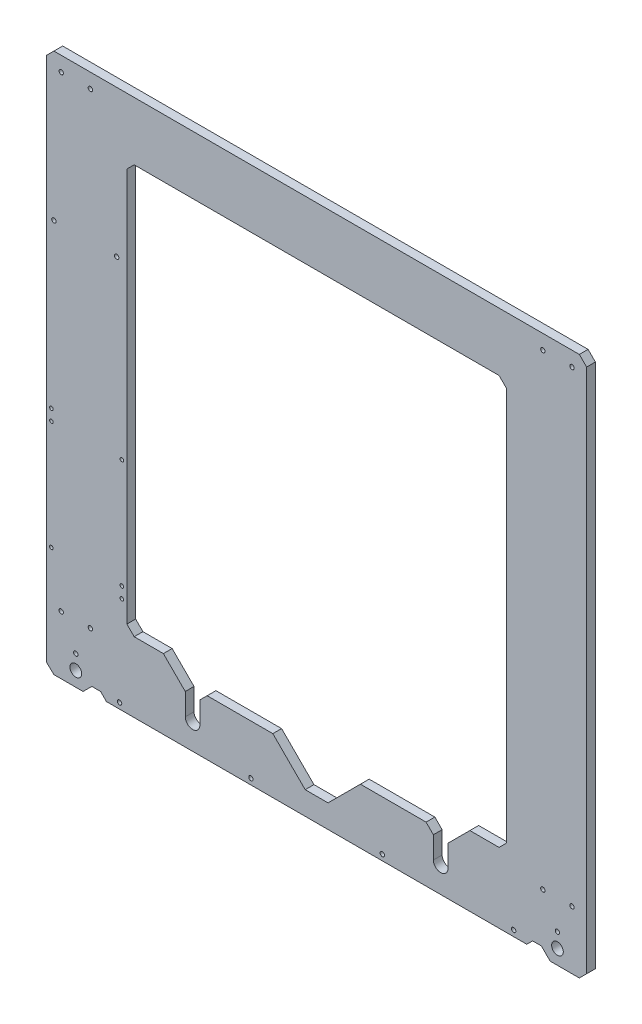
SolidWorks part; units mm, degrees
material "Lega 1060"
ref_plane "Piano frontale" through (0, 0, 0) normal (0, 0, 1) x (1, 0, 0)
ref_plane "Piano superiore" through (0, 0, 0) normal (0, 1, 0) x (1, 0, 0)
ref_plane "Piano destro" through (0, 0, 0) normal (1, 0, 0) x (0, 0, -1)
sketch "FRAME" plane through (0, 0, 0) normal (0, 0, 1) x (1, 0, 0)
  line L0 (0, 4.8083) -> (0, 365)
  line L1 (5, 370) -> (365, 370)
  line L2 (370, 365) -> (370, 5)
  line L3 (365, 0) -> (345, 0)
  line L4 (5, 0) -> (0, 4.8083)
  line L5 (0, 4.8083) -> (0, 365)
  line L6 (0, 365) -> (5, 370)
  line L7 (5, 370) -> (365, 370)
  line L8 (365, 370) -> (370, 365)
  line L9 (370, 365) -> (370, 5)
  line L10 (370, 5) -> (365, 0)
  line L11 (365, 0) -> (345, 0)
  line L12 (345, 0) -> (343, 2)
  line L13 (329, 2) -> (41, 2)
  line L14 (27, 2) -> (25, 0)
  line L15 (25, 0) -> (5, 0)
  line L16 (95, 20) -> (95, 35)
  line L17 (95, 35) -> (80, 50)
  line L18 (80, 50) -> (60, 50)
  line L19 (60, 50) -> (55, 55)
  line L20 (55, 55) -> (55, 325)
  line L21 (55, 325) -> (60, 330)
  line L22 (60, 330) -> (310, 330)
  line L23 (310, 330) -> (315, 325)
  line L24 (315, 325) -> (315, 55)
  line L25 (315, 55) -> (310, 50)
  line L26 (105, 20) -> (105, 35)
  line L27 (105, 35) -> (110, 40)
  line L28 (310, 50) -> (290, 50)
  line L29 (290, 50) -> (275, 35)
  line L30 (275, 35) -> (275, 20)
  line L31 (265, 20) -> (265, 35)
  line L32 (265, 35) -> (260, 40)
  line L33 (177.1751, 17.8249) -> (192.8249, 17.8249)
  line L34 (192.8249, 17.8249) -> (215, 40)
  line L35 (177.1751, 17.8249) -> (155, 40)
  line L36 (110, 40) -> (155, 40)
  line L37 (215, 40) -> (260, 40)
  line L105 (340, 360) -> (360, 360) construction
  line L178 (343, 2) -> (339, 6)
  line L179 (339, 6) -> (333, 6)
  line L180 (333, 6) -> (329, 2)
  line L181 (27, 2) -> (31, 6)
  line L182 (31, 6) -> (37, 6)
  line L183 (37, 6) -> (41, 2)
  line L196 (25, 0) -> (5, 0)
  line L198 (355, 0) -> (404.0551, 0) construction
  line L199 (290, 370) -> (404.0551, 370) construction
  arc A0 (95, 20) -> (105, 20) centre (100, 20) ccw
  arc A1 (265, 20) -> (275, 20) centre (270, 20) ccw
  circle A2 centre (3.2951, 74.61) radius 1.25
  circle A3 centre (51.5551, 150.81) radius 1.25
  circle A4 centre (3.2951, 157.16) radius 1.25
  circle A5 centre (3.2951, 149.54) radius 1.25
  circle A16 centre (50, 6) radius 1.5
  circle A17 centre (320, 6) radius 1.5
  circle A18 centre (230, 6) radius 1.5
  circle A19 centre (140, 6) radius 1.5
  circle A20 centre (20, 10) radius 4
  circle A21 centre (350, 10) radius 4
  circle A26 centre (10, 40) radius 1.5
  circle A27 centre (30, 40) radius 1.5
  circle A28 centre (20, 20) radius 1.5
  circle A29 centre (350, 20) radius 1.5
  circle A30 centre (340, 40) radius 1.5
  circle A31 centre (360, 40) radius 1.5
  circle A32 centre (360, 360) radius 1.5
  circle A33 centre (340, 360) radius 1.5
  circle A34 centre (10, 360) radius 1.5
  circle A35 centre (30, 360) radius 1.5
  circle A46 centre (51.5551, 75.88) radius 1.25
  circle A47 centre (51.5551, 68.26) radius 1.25
  circle A50 centre (5, 269.5) radius 1.5
  circle A51 centre (48, 269.5) radius 1.5
  point P0 (51.5551, 150.81)
  point P1 (3.2951, 149.54)
  point P2 (51.5551, 68.26)
  point P3 (3.2951, 74.61)
  point P194 (3.2951, 157.16)
  point P195 (51.5551, 75.88)
  dimension "D8" = 370
sketch "ANCORS" [suppressed] plane through (0, 0, 0) normal (0, 0, 1) x (1, 0, 0)
  line L1 (170.0247, 235) -> (170.0247, 194) construction
  line L2 (170.0247, 214.5) -> (158.9936, 214.5) construction
  circle A0 centre (120.7826, 212.556) radius 2
  circle A1 centre (216.1502, 212.556) radius 2
  circle A2 centre (167.2683, 270.0641) radius 2
  circle A3 centre (167.2683, 156.9648) radius 2
  circle A4 centre (120.7826, 90.4425) radius 2
  circle A5 centre (216.1502, 90.4425) radius 2
  circle A6 centre (170.0247, 214.5) radius 2
  dimension "D1" = 4
extrude "Boss-Extrude1" add sketch "FRAME" along normal blind 6 contours L182 L183 L13 L180 L179 L178 L12 L3 L10 L2 L8 L1 L6 L0 L4 L15 L14 L181 A51 A50 A47 A46 A35 A34 A33 A32 A31 A30 A29 A28 A27 A26 A21 A20 region at (5.2326, 184.9041, 0)
